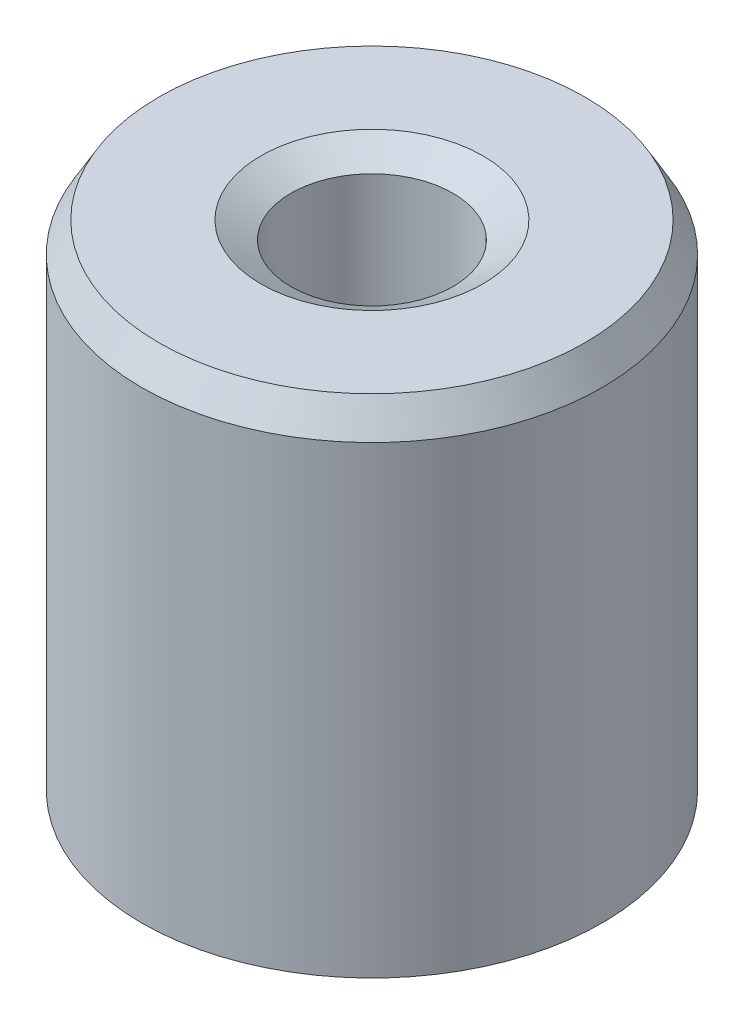
SolidWorks part; units mm, degrees
ref_plane "Front Plane" through (0, 0, 0) normal (0, 0, 1) x (1, 0, 0)
ref_plane "Top Plane" through (0, 0, 0) normal (0, 1, 0) x (1, 0, 0)
ref_plane "Right Plane" through (0, 0, 0) normal (1, 0, 0) x (0, 0, -1)
sketch "Sketch1" plane through (0, 0, 0) normal (0, 1, 0) x (1, 0, 0)
  circle A0 centre (0, 0) radius 10
  dimension "SLEEVE_OD" = 20
extrude "Boss-Extrude1" add sketch "Sketch1" along normal blind 22.1942
sketch "Sketch2" plane through (0, 0, 0) normal (0, 1, 0) x (1, 0, 0)
  circle A0 centre (0, 0) radius 3.5168
  dimension "BORE_D" = 7.0337
extrude "Cut-Extrude1" cut sketch "Sketch2" along normal through all
chamfer "Chamfer1" distance 1.3042 angle 30 4 edges at (0, 22.1942, 3.5168) (0, 0, 3.5168) (0, 0, 10) (0, 22.1942, 10) first distance on face at (0, 22.1942, 3.5168) first distance on face at (0, 0, 3.5168) first distance on face at (0, 22.1942, 10)
